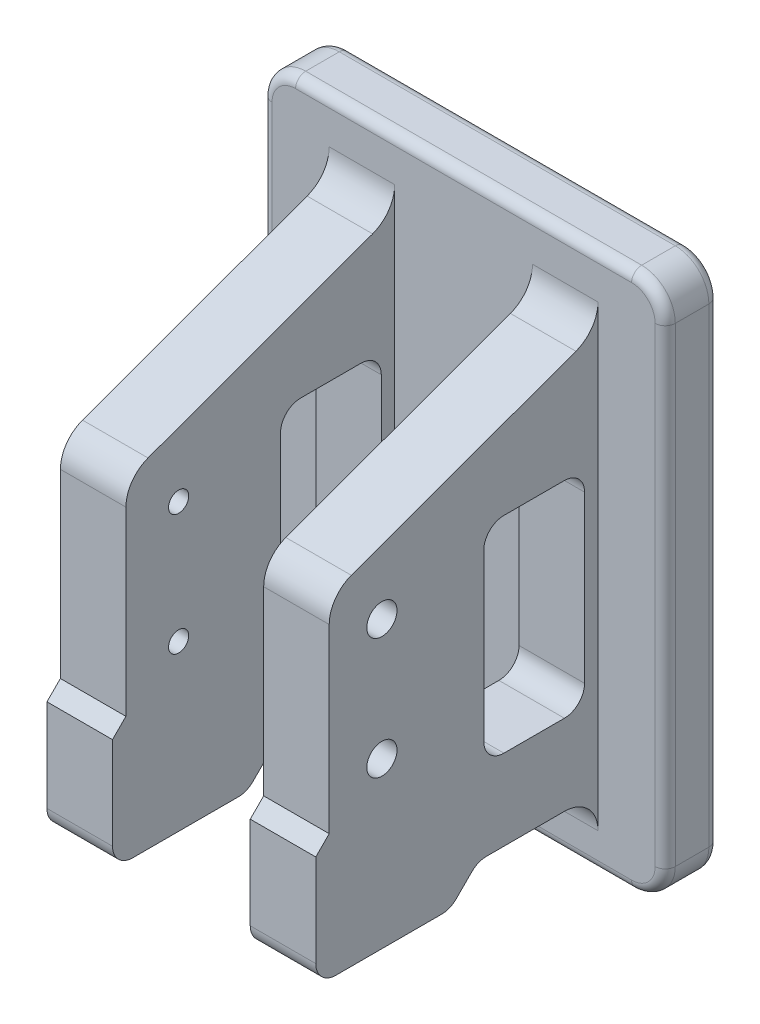
SolidWorks part; units mm, degrees
ref_plane "Front Plane" through (0, 0, 0) normal (0, 0, 1) x (1, 0, 0)
ref_plane "Top Plane" through (0, 0, 0) normal (0, 1, 0) x (1, 0, 0)
ref_plane "Right Plane" through (0, 0, 0) normal (1, 0, 0) x (0, 0, -1)
sketch "Sketch3" plane through (0, 0, 30) normal (0, 0, -1) x (-1, 0, 0)
  line L0 (95, 33.2573) -> (65, 33.2573) construction
  line L15 (80, 53.2573) -> (80, 33.2573) construction
  line L20 (55, 53.2573) -> (105, 53.2573)
  line L29 (55, -26.7427) -> (105, -26.7427)
  line L31 (110, -21.7427) -> (110, 48.2573)
  line L33 (50, -21.7427) -> (50, 48.2573)
  arc A17 (50, 48.2573) -> (55, 53.2573) centre (55, 48.2573) cw
  arc A18 (110, 48.2573) -> (105, 53.2573) centre (105, 48.2573) ccw
  arc A21 (50, -21.7427) -> (55, -26.7427) centre (55, -21.7427) ccw
  arc A22 (110, -21.7427) -> (105, -26.7427) centre (105, -21.7427) cw
  dimension "D1" = 5
extrude "Boss-Extrude1" add sketch "Sketch3" along normal blind 8
sketch "Sketch8" plane through (0, 0, 22) normal (0, 0, -1) x (-1, 0, 0)
  line L0 (50, 13.2573) -> (110, 13.2573) construction
  line L1 (50, 48.2573) -> (50, -21.7427) construction
  line L2 (110, -21.7427) -> (110, 48.2573) construction
  line L3 (80, 13.2573) -> (80, -26.7427) construction
  line L4 (55, -26.7427) -> (105, -26.7427) construction
  line L5 (78.25, 15.3786) -> (78.25, 11.136)
  line L6 (81.75, 15.3786) -> (81.75, 11.136)
  arc A0 (78.25, 11.136) -> (81.75, 11.136) centre (80, 13.2573) ccw
  arc A1 (81.75, 15.3786) -> (78.25, 15.3786) centre (80, 13.2573) ccw
extrude "Cut-Extrude3" cut sketch "Sketch8" against normal blind 3
sketch "Sketch10" plane through (0, 0, 22) normal (0, 0, -1) x (-1, 0, 0)
  line L0 (50, 13.2573) -> (110, 13.2573) construction
  line L1 (50, 48.2573) -> (50, -21.7427) construction
  line L2 (110, -21.7427) -> (110, 48.2573) construction
  line L3 (80, 13.2573) -> (80, -26.7427) construction
  line L4 (55, -26.7427) -> (105, -26.7427) construction
  line L7 (81.75, 11.136) -> (81.75, 15.3786)
  line L8 (78.25, 15.3786) -> (78.25, 11.136)
  line L9 (81.75, 11.136) -> (81.75, 15.3786)
  line L10 (78.25, 15.3786) -> (78.25, 11.136)
  circle A3 centre (80, 13.2573) radius 9.75
  arc A5 (78.25, 11.136) -> (81.75, 11.136) centre (80, 13.2573) ccw
  arc A6 (81.75, 15.3786) -> (78.25, 15.3786) centre (80, 13.2573) ccw
  arc A7 (78.25, 11.136) -> (81.75, 11.136) centre (80, 13.2573) ccw
  arc A8 (81.75, 15.3786) -> (78.25, 15.3786) centre (80, 13.2573) ccw
  dimension "D1" = 0
extrude "Boss-Extrude4" add sketch "Sketch10" along normal blind 9
fillet "Fillet2" radius 1.5 16 edges at (-80, -26.7427, 30) (-80, 53.2573, 30) (-50, 13.2573, 30) (-51.4645, 51.7928, 30) (-108.5355, 51.7928, 30) (-110, 13.2573, 30) (-80, -26.7427, 22) (-50, 13.2573, 22) (-51.4645, 51.7928, 22) (-80, 53.2573, 22) (-108.5355, 51.7928, 22) (-110, 13.2573, 22) (-108.5355, -25.2783, 22) (-51.4645, -25.2783, 22) (-108.5355, -25.2783, 30) (-51.4645, -25.2783, 30)
sketch "Sketch11" plane through (0, 0, 22) normal (0, 0, -1) x (-1, 0, 0)
  line L0 (50, 13.2573) -> (110, 13.2573) construction
  line L1 (50, -21.7427) -> (50, 48.2573) construction
  line L2 (110, 48.2573) -> (110, -21.7427) construction
  line L3 (80, 13.2573) -> (80, -26.7427) construction
  line L4 (105, -26.7427) -> (55, -26.7427) construction
  circle A0 centre (80, 13.2573) radius 11.75
extrude "Boss-Extrude5" add sketch "Sketch11" along normal blind 1
sketch "Sketch14" plane through (-70, 0, 0) normal (1, 0, 0) x (0, 0, -1)
  line L0 (-22, 1.5073) -> (-22, 25.0073) construction
  line L1 (-30, 48.2573) -> (-30, -21.7427) construction
  line L2 (-70, -1.7605) -> (-70, 28.6985)
  line L3 (-70, 28.6985) -> (-30, 43.2573)
  line L4 (-30, -16.3789) -> (-47.8764, -16.3789)
  line L6 (-30, -16.3789) -> (-30, 43.2573)
  line L7 (-47.8764, -16.3789) -> (-52, -20.5025)
  line L8 (-52, -20.5025) -> (-72, -20.5025)
  line L9 (-72, -20.5025) -> (-72, -3.7605)
  line L11 (-72, -3.7605) -> (-70, -1.7605)
  circle A6 centre (-62.1572, 3.9815) radius 1.5 construction
  circle A7 centre (-62.1572, 21.9815) radius 1.5 construction
  circle A8 centre (-62.1572, 3.9815) radius 1.5
  circle A9 centre (-62.1572, 21.9815) radius 1.5
extrude "Boss-Extrude7" add sketch "Sketch14" along normal blind 10
sketch "Sketch15" plane through (-90, 0, 0) normal (-1, 0, 0) x (0, 0, 1)
  line L4 (47.8764, -16.3789) -> (52, -20.5025)
  line L5 (70, -1.7605) -> (70, 28.6985)
  line L6 (70, 28.6985) -> (30, 43.2573)
  line L7 (30, 43.2573) -> (30, -16.3789)
  line L9 (70, -1.7605) -> (70, 28.6985)
  line L10 (70, 28.6985) -> (30, 43.2573)
  line L15 (30, 43.2573) -> (30, -16.3789)
  line L20 (47.8764, -16.3789) -> (52, -20.5025)
  line L21 (52, -20.5025) -> (72, -20.5025)
  line L22 (52, -20.5025) -> (72, -20.5025)
  line L23 (72, -20.5025) -> (72, -3.7605)
  line L24 (72, -20.5025) -> (72, -3.7605)
  line L25 (72, -3.7605) -> (70, -1.7605)
  line L26 (72, -3.7605) -> (70, -1.7605)
  line L27 (30, -16.3789) -> (47.8764, -16.3789)
  line L28 (30, -16.3789) -> (47.8764, -16.3789)
  circle A2 centre (62.1572, 3.9815) radius 1.5 construction
  circle A3 centre (62.1572, 21.9815) radius 1.5 construction
  circle A4 centre (62.1572, 3.9815) radius 1.5
  circle A5 centre (62.1572, 21.9815) radius 1.5
  dimension "D1" = 0
extrude "Boss-Extrude8" add sketch "Sketch15" along normal blind 10
fillet "Fillet3" radius 5 6 edges at (-65, 43.2573, 30) (-95, 43.2573, 30) (-95, 28.6985, 70) (-65, 28.6985, 70) (-95, -16.3789, 30) (-65, -16.3789, 30)
fillet "Fillet4" radius 3 6 edges at (-95, -20.5025, 72) (-65, -20.5025, 72) (-65, -20.5025, 52) (-95, -20.5025, 52) (-95, -16.3789, 47.8764) (-65, -16.3789, 47.8764)
sketch "Sketch16" plane through (-90, 0, 0) normal (1, 0, 0) x (0, 0, -1)
  line L8 (-72, -3.7605) -> (-72, -17.5025)
  line L9 (-69, -20.5025) -> (-53.2426, -20.5025)
  line L10 (-51.1213, -19.6238) -> (-48.7551, -17.2576)
  line L11 (-46.6337, -16.3789) -> (-35, -16.3789)
  line L12 (-30, -21.3789) -> (-30, 46.7583)
  line L13 (-33.2899, 42.0599) -> (-66.7101, 29.8959)
  line L14 (-70, 25.1974) -> (-70, -1.7605)
  line L15 (-70, -1.7605) -> (-72, -3.7605)
  line L16 (-72, -3.7605) -> (-72, -17.5025)
  line L17 (-69, -20.5025) -> (-53.2426, -20.5025)
  line L18 (-51.1213, -19.6238) -> (-48.7551, -17.2576)
  line L19 (-46.6337, -16.3789) -> (-35, -16.3789)
  line L20 (-30, -21.3789) -> (-30, 46.7583)
  line L21 (-33.2899, 42.0599) -> (-66.7101, 29.8959)
  line L22 (-70, 25.1974) -> (-70, -1.7605)
  line L23 (-70, -1.7605) -> (-72, -3.7605)
  arc A6 (-72, -17.5025) -> (-69, -20.5025) centre (-69, -17.5025) ccw
  arc A7 (-53.2426, -20.5025) -> (-51.1213, -19.6238) centre (-53.2426, -17.5025) ccw
  arc A8 (-46.6337, -16.3789) -> (-48.7551, -17.2576) centre (-46.6337, -19.3789) ccw
  arc A9 (-30, -21.3789) -> (-35, -16.3789) centre (-35, -21.3789) ccw
  arc A10 (-33.2899, 42.0599) -> (-30, 46.7583) centre (-35, 46.7583) ccw
  arc A11 (-66.7101, 29.8959) -> (-70, 25.1974) centre (-65, 25.1974) ccw
  arc A12 (-72, -17.5025) -> (-69, -20.5025) centre (-69, -17.5025) ccw
  arc A13 (-53.2426, -20.5025) -> (-51.1213, -19.6238) centre (-53.2426, -17.5025) ccw
  arc A14 (-46.6337, -16.3789) -> (-48.7551, -17.2576) centre (-46.6337, -19.3789) ccw
  arc A15 (-30, -21.3789) -> (-35, -16.3789) centre (-35, -21.3789) ccw
  arc A16 (-33.2899, 42.0599) -> (-30, 46.7583) centre (-35, 46.7583) ccw
  arc A17 (-66.7101, 29.8959) -> (-70, 25.1974) centre (-65, 25.1974) ccw
  dimension "D1" = 0
extrude "Cut-Extrude4" cut sketch "Sketch16" against normal blind 0.25
sketch "Sketch17" plane through (-70, 0, 0) normal (-1, 0, 0) x (0, 0, 1)
  line L8 (53.2426, -20.5025) -> (69, -20.5025)
  line L9 (72, -17.5025) -> (72, -3.7605)
  line L10 (72, -3.7605) -> (70, -1.7605)
  line L11 (70, -1.7605) -> (70, 25.1974)
  line L12 (66.7101, 29.8959) -> (33.2899, 42.0599)
  line L13 (30, 46.7583) -> (30, -21.3789)
  line L14 (35, -16.3789) -> (46.6337, -16.3789)
  line L15 (48.7551, -17.2576) -> (51.1213, -19.6238)
  line L16 (53.2426, -20.5025) -> (69, -20.5025)
  line L17 (72, -17.5025) -> (72, -3.7605)
  line L18 (72, -3.7605) -> (70, -1.7605)
  line L19 (70, -1.7605) -> (70, 25.1974)
  line L20 (66.7101, 29.8959) -> (33.2899, 42.0599)
  line L21 (30, 46.7583) -> (30, -21.3789)
  line L22 (35, -16.3789) -> (46.6337, -16.3789)
  line L23 (48.7551, -17.2576) -> (51.1213, -19.6238)
  arc A6 (69, -20.5025) -> (72, -17.5025) centre (69, -17.5025) ccw
  arc A7 (70, 25.1974) -> (66.7101, 29.8959) centre (65, 25.1974) ccw
  arc A8 (30, 46.7583) -> (33.2899, 42.0599) centre (35, 46.7583) ccw
  arc A9 (35, -16.3789) -> (30, -21.3789) centre (35, -21.3789) ccw
  arc A10 (48.7551, -17.2576) -> (46.6337, -16.3789) centre (46.6337, -19.3789) ccw
  arc A11 (51.1213, -19.6238) -> (53.2426, -20.5025) centre (53.2426, -17.5025) ccw
  arc A12 (69, -20.5025) -> (72, -17.5025) centre (69, -17.5025) ccw
  arc A13 (70, 25.1974) -> (66.7101, 29.8959) centre (65, 25.1974) ccw
  arc A14 (30, 46.7583) -> (33.2899, 42.0599) centre (35, 46.7583) ccw
  arc A15 (35, -16.3789) -> (30, -21.3789) centre (35, -21.3789) ccw
  arc A16 (48.7551, -17.2576) -> (46.6337, -16.3789) centre (46.6337, -19.3789) ccw
  arc A17 (51.1213, -19.6238) -> (53.2426, -20.5025) centre (53.2426, -17.5025) ccw
  dimension "D1" = 0
extrude "Cut-Extrude5" cut sketch "Sketch17" against normal blind 0.25
sketch "Sketch18" plane through (-100, 0, 0) normal (-1, 0, 0) x (0, 0, 1)
  line L0 (23.5, 53.2573) -> (28.5, 53.2573) construction
  line L1 (35, 26.2573) -> (44, 26.2573)
  line L2 (32, 23.2573) -> (32, -1.3789)
  line L3 (35, -4.3789) -> (44, -4.3789)
  line L4 (47, 23.2573) -> (47, -1.3789)
  line L5 (35, -16.3789) -> (46.6337, -16.3789) construction
  line L6 (30, 48.2573) -> (30, -21.7427) construction
  arc A0 (44, -4.3789) -> (47, -1.3789) centre (44, -1.3789) ccw
  arc A1 (32, -1.3789) -> (35, -4.3789) centre (35, -1.3789) ccw
  arc A2 (35, 26.2573) -> (32, 23.2573) centre (35, 23.2573) ccw
  arc A3 (44, 26.2573) -> (47, 23.2573) centre (44, 23.2573) cw
  point P16 (32, 26.2573)
  point P19 (47, 26.2573)
  dimension "D5" = 3
  dimension "D1" = 27
  dimension "D2" = 12
  dimension "D3" = 15
  dimension "D4" = 2
extrude "Cut-Extrude6" cut sketch "Sketch18" against normal up to surface (40 mm away) up to face at (-60, -0.7658, 53.3813)
sketch "Sketch19" plane through (-60, 0, 0) normal (1, 0, 0) x (0, 0, -1)
  circle A0 centre (-62.1572, 21.9815) radius 2.25
  circle A1 centre (-62.1572, 3.9815) radius 2.25
extrude "Cut-Extrude7" cut sketch "Sketch19" against normal blind 4
chamfer "Chamfer1" distance 1.5 angle 45 2 edges at (-100, 2.4815, 62.1572) (-100, 20.4815, 62.1572)
